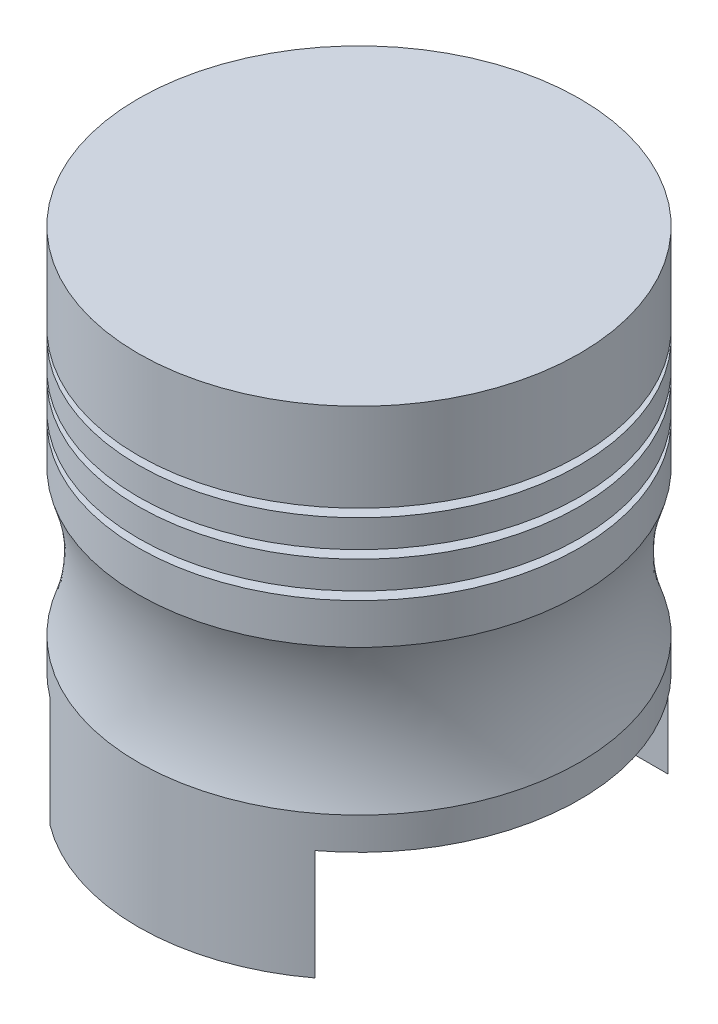
SolidWorks part; units mm, degrees
ref_plane "Front Plane" through (0, 0, 0) normal (0, 0, 1) x (1, 0, 0)
ref_plane "Top Plane" through (0, 0, 0) normal (0, 1, 0) x (1, 0, 0)
ref_plane "Right Plane" through (0, 0, 0) normal (1, 0, 0) x (0, 0, -1)
sketch "Sketch2" plane through (0, 0, 0) normal (1, 0, 0) x (0, 0, -1)
  line L0 (0, 126.1061) -> (40, 126.1061)
  line L5 (0, 126.1061) -> (0, 56.1061)
  line L9 (40, 56.1061) -> (40, 126.1061)
  line L10 (40, 56.1061) -> (0, 56.1061)
  dimension "D1" = 40
  dimension "D4" = 70
  dimension "D5" = 40
revolve "Revolve1" add sketch "Sketch2" angle 360 about L5
sketch "Sketch3" plane through (0, 0, 0) normal (1, 0, 0) x (0, 0, -1)
  line L1 (-40, 126.1061) -> (-40, 56.1061) construction
  line L7 (-32, 56.1061) -> (-14.4568, 56.1061)
  line L8 (32, 56.1061) -> (14.4568, 56.1061)
  line L9 (-40, 56.1061) -> (40, 56.1061) construction
  line L10 (-14.4568, 56.1061) -> (14.4568, 56.1061)
  line L12 (-32, 56.1061) -> (-32, 36.1061)
  line L13 (32, 56.1061) -> (32, 36.1061)
  arc A1 (-12.1715, 42.253) -> (12.1715, 42.253) centre (0, 51.0197) ccw
  arc A4 (-32, 36.1061) -> (-19.6245, 43.0006) centre (-40, 65.0197) ccw
  arc A6 (19.6245, 43.0006) -> (32, 36.1061) centre (40, 65.0197) ccw
  arc A7 (19.6245, 43.0006) -> (12.1715, 42.253) centre (16.2286, 39.3308) ccw
  arc A8 (-12.1715, 42.253) -> (-19.6245, 43.0006) centre (-16.2286, 39.3308) ccw
  circle A9 centre (0, 45.4171) radius 5
  dimension "D5" = 30
  dimension "D1" = 15
  dimension "D6" = 30
  dimension "D7" = 5
  dimension "D4" = 10
  dimension "D2" = 20
  dimension "D3" = 20
sketch "Sketch4" plane through (0, 0, 0) normal (1, 0, 0) x (0, 0, -1)
  line L0 (40, 56.1061) -> (40, 36.1061)
  line L1 (40, 56.1061) -> (0, 56.1061)
  line L2 (-40, 56.1061) -> (40, 56.1061) construction
  line L3 (0, 56.1061) -> (0, 36.1061)
  line L4 (0, 36.1061) -> (40, 36.1061)
  dimension "D1" = 20
revolve "Revolve2" add sketch "Sketch4" angle 360 about L3
sketch "Sketch5" plane through (0, 0, 0) normal (1, 0, 0) x (0, 0, -1)
  line L0 (32, 36.1061) -> (32, 56.1061)
  line L1 (-40, 36.1061) -> (40, 36.1061) construction
  line L2 (32, 56.1061) -> (-32, 56.1061)
  line L3 (-32, 56.1061) -> (-32, 36.1061)
  line L4 (-32, 36.1061) -> (32, 36.1061)
  dimension "D1" = 20
  dimension "D2" = 64
  dimension "D3" = 8
extrude "Cut-Extrude1" cut sketch "Sketch5" against normal blind 47 and the other way blind 51
extrude "Boss-Extrude1" add sketch "Sketch3" along normal blind 4 and the other way blind 4
fillet "Fillet2" radius 5 1 edges at (4, 46.1061, 32)
fillet "Fillet3" radius 5 3 edges at (-4, 46.1061, 32) (-4, 46.1061, -32) (4, 46.1061, -32)
sketch "Sketch7" plane through (0, 56.1061, 0) normal (0, -1, 0) x (1, 0, 0)
  line L6 (-4, -22) -> (-4, 22)
  line L8 (9, -27) -> (22.7597, -27)
  line L9 (9, 27) -> (22.7597, 27)
  line L10 (-22.7597, -27) -> (-9, -27)
  line L11 (-22.7597, 27) -> (-9, 27)
  line L13 (4, -22) -> (4, 22)
  arc A0 (-26.5944, -25.2087) -> (-26.5944, 25.2087) centre (3.532, 0) cw
  arc A5 (26.5944, -25.2087) -> (26.5944, 25.2087) centre (-3.532, 0) ccw
  arc A7 (-22.7597, 27) -> (-26.5944, 25.2087) centre (-22.7597, 22) ccw
  arc A8 (-26.5944, -25.2087) -> (-22.7597, -27) centre (-22.7597, -22) ccw
  arc A9 (-9, -27) -> (-4, -22) centre (-9, -22) ccw
  arc A10 (9, -27) -> (4, -22) centre (9, -22) cw
  arc A11 (4, 22) -> (9, 27) centre (9, 22) cw
  arc A12 (-4, 22) -> (-9, 27) centre (-9, 22) ccw
  arc A13 (22.7597, 27) -> (26.5944, 25.2087) centre (22.7597, 22) cw
  arc A14 (22.7597, -27) -> (26.5944, -25.2087) centre (22.7597, -22) ccw
  point P11 (-25, -27)
  point P19 (-4, -27)
  point P26 (4, -27)
  point P29 (4, 27)
  point P32 (-4, 27)
  point P35 (25, 27)
  point P38 (25, -27)
  dimension "D3" = 21
  dimension "D5" = 5
  dimension "D1" = 21
extrude "Cut-Extrude2" cut sketch "Sketch7" against normal blind 60
sketch "Sketch8" plane through (0, 0, 0) normal (1, 0, 0) x (0, 0, -1)
  line L0 (40, 110.1061) -> (37, 110.1061)
  line L1 (40, 36.1061) -> (40, 126.1061) construction
  line L2 (37, 110.1061) -> (37, 108.6061)
  line L3 (37, 108.6061) -> (40, 108.6061)
  line L4 (40, 126.1061) -> (-40, 126.1061) construction
  line L5 (40, 103.6061) -> (37, 103.6061)
  line L6 (37, 103.6061) -> (37, 102.1061)
  line L7 (37, 102.1061) -> (40, 102.1061)
  line L8 (40, 61.9418) -> (40, 88.2704)
  line L9 (40, 97.1061) -> (37, 97.1061)
  line L10 (37, 97.1061) -> (37, 95.6061)
  line L11 (37, 95.6061) -> (40, 95.6061)
  line L12 (40, 95.6061) -> (40, 97.1061)
  line L13 (40, 102.1061) -> (40, 103.6061)
  line L14 (40, 108.6061) -> (40, 110.1061)
  line L15 (0, 45.4171) -> (0, 126.1061)
  arc A0 (40, 88.2704) -> (40, 61.9418) centre (76.7111, 75.1061) ccw
  dimension "D10" = 78
  dimension "D1" = 1.5
  dimension "D2" = 5
  dimension "D3" = 1.5
  dimension "D4" = 5
  dimension "D5" = 1.5
  dimension "D6" = 16
  dimension "D7" = 51
  dimension "D9" = 3
revolve "Cut-Revolve1" cut sketch "Sketch8" angle 360 about L15
